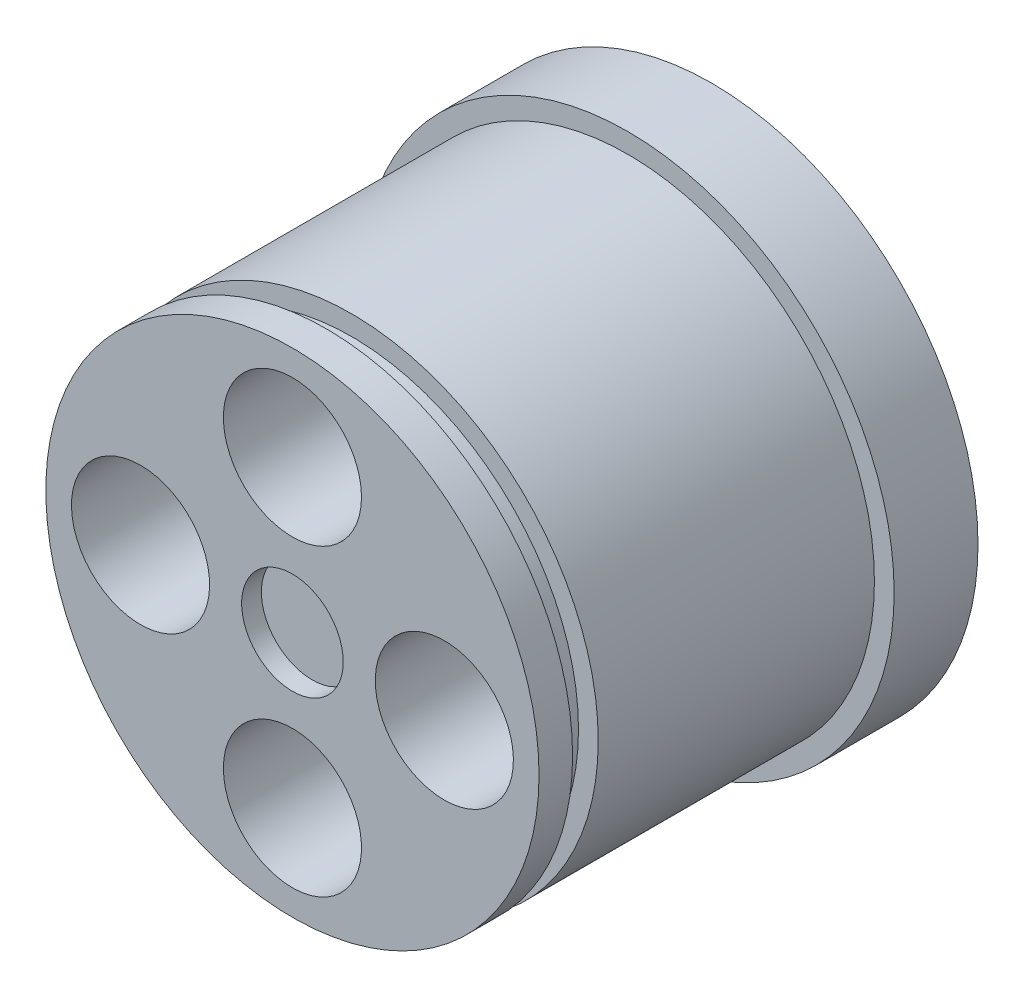
SolidWorks part; units mm, degrees
ref_plane "Front Plane" through (0, 0, 0) normal (0, 0, 1) x (1, 0, 0)
ref_plane "Top Plane" through (0, 0, 0) normal (0, 1, 0) x (1, 0, 0)
ref_plane "Right Plane" through (0, 0, 0) normal (1, 0, 0) x (0, 0, -1)
ref_axis "Z" through (0, 0, 10.5) along (0, 0, -1)
sketch "Sketch1" plane through (0, 0, 0) normal (0, 0, 1) x (1, 0, 0)
  circle A0 centre (0, 0) radius 12.5
  dimension "D1" = 25
extrude "Boss-Extrude1" add sketch "Sketch1" along normal blind 17
sketch "Sketch2" plane through (0, 0, 0) normal (0, 0, 1) x (1, 0, 0)
  circle A0 centre (0, 0) radius 13.5
  dimension "D1" = 27
extrude "Boss-Extrude2" add sketch "Sketch2" against normal blind 4.25
ref_plane "Plane1" through (0, 0, 14.65) normal (0, 0, 1) x (1, 0, 0)
sketch "Sketch3" plane through (0, 0, 14.65) normal (0, 0, 1) x (1, 0, 0)
  circle A0 centre (0, 0) radius 11.5
  circle A1 centre (0, 0) radius 58.2437
  dimension "D1" = 23
extrude "RetainingRingGroove" cut sketch "Sketch3" against normal blind 0.65 and the other way blind 0.65
sketch "Sketch4" plane through (0, 0, 17) normal (0, 0, 1) x (1, 0, 0)
  circle A0 centre (0, 0) radius 2.575
  dimension "D1" = 5.15
extrude "MagnetSlot" cut sketch "Sketch4" against normal blind 1
sketch "Sketch6" plane through (0, 0, 17) normal (0, 0, 1) x (1, 0, 0)
  line L0 (0, 0) -> (0, 7.7) construction
  line L2 (-1.4722, 10.25) -> (-2.9445, 7.7)
  line L3 (-2.9445, 7.7) -> (-1.4722, 5.15)
  line L4 (-1.4722, 5.15) -> (1.4722, 5.15)
  line L5 (1.4722, 5.15) -> (2.9445, 7.7)
  line L6 (2.9445, 7.7) -> (1.4722, 10.25)
  line L7 (1.4722, 10.25) -> (-1.4722, 10.25)
  circle A0 centre (0, 7.7) radius 2.55 construction
  dimension "D1" = 7.7
  dimension "D2" = 5.1
extrude "NutCut" cut sketch "Sketch6" against normal offset from surface (17.25 mm away) 4 up to face at (13.5, 0, -4.25)
sketch "Sketch7" plane through (0, 0, 17) normal (0, 0, 1) x (1, 0, 0)
  circle A0 centre (0, 7.7) radius 3.5
  dimension "D1" = 7
extrude "NutHole" cut sketch "Sketch7" against normal blind 15
sketch "Sketch8" plane through (0, 0, 17) normal (0, 0, 1) x (1, 0, 0)
  circle A0 centre (0, 7.7) radius 1.35
  dimension "D1" = 2.7
extrude "ScrewHole" cut sketch "Sketch8" against normal through all both and the other way through all
pattern_circular "CirPattern1" count 4 over 360 about axis through (0, 0, 10.5) along (0, 0, -1) of "MagnetSlot", "NutCut", "NutHole", "ScrewHole"
